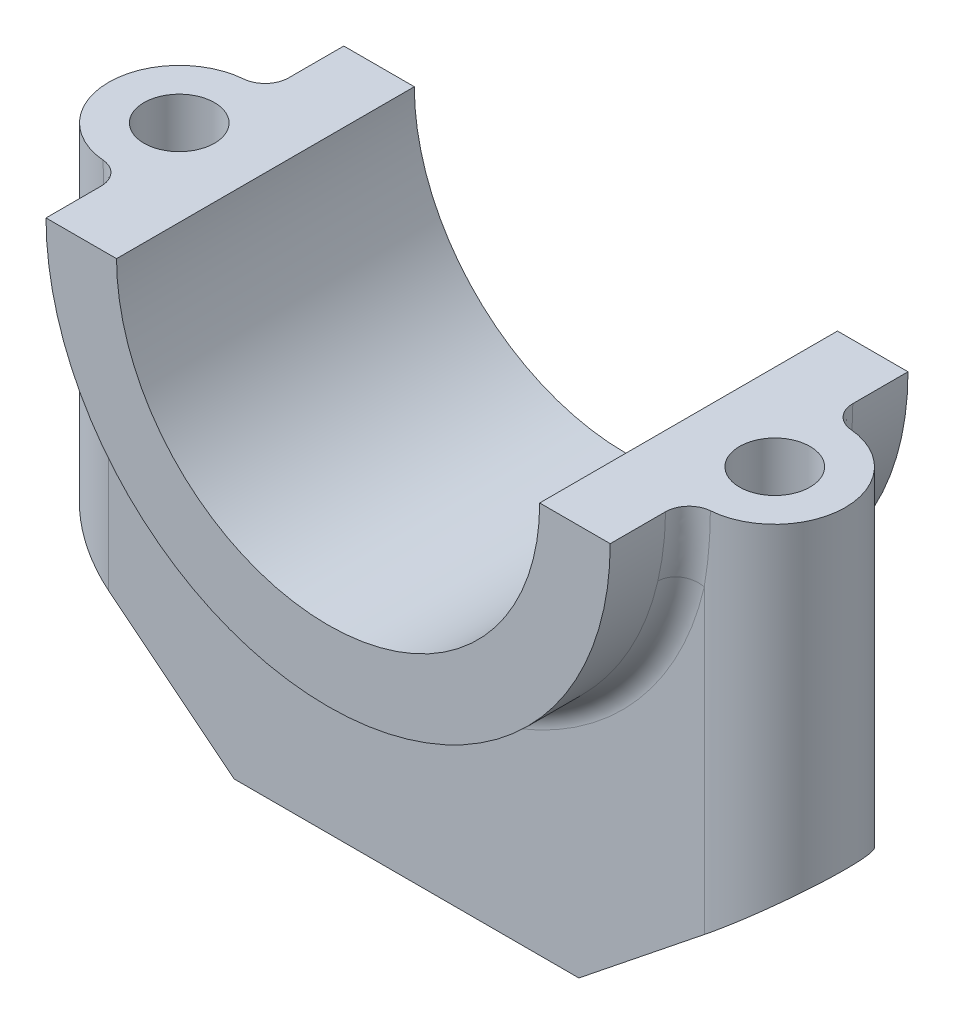
SolidWorks part; units mm, degrees
ref_plane "Front Plane" through (0, 0, 0) normal (0, 0, 1) x (1, 0, 0)
ref_plane "Top Plane" through (0, 0, 0) normal (0, 1, 0) x (1, 0, 0)
ref_plane "Right Plane" through (0, 0, 0) normal (1, 0, 0) x (0, 0, -1)
sketch "Sketch1" plane through (0, 0, 0) normal (0, 0, 1) x (1, 0, 0)
  line L0 (0, 0) -> (0, 17141.6634) construction
  line L1 (0, 0) -> (17141.6634, 0) construction
  line L2 (-47, 0) -> (47, 0)
  line L3 (47, 0) -> (47, -40)
  line L4 (47, -40) -> (22, -60)
  line L5 (22, -60) -> (-22, -60)
  line L6 (-47, -40) -> (-22, -60)
  line L7 (-47, 0) -> (-47, -40)
  arc A0 (-36, 0) -> (36, 0) centre (0, 0) ccw
  arc A1 (-27, 0) -> (27, 0) centre (0, 0) ccw
  point P11 (0, 0)
  point P15 (0, -60)
  point P16 (-1.8209, -32.4049)
  dimension "D1" = 72
  dimension "D2" = 54
  dimension "D3" = 25
  dimension "D4" = 60
  dimension "D5" = 20
  dimension "D6" = 47
extrude "Boss-Extrude1" add sketch "Sketch1" along normal mid plane 38 contours A1 L2 A0 region at (-31.5, -0.805, 0)
extrude "Boss-Extrude2" add sketch "Sketch1<3>" along normal mid plane 18 contours A0 L2 L7 L6 L5 L4 L3 region at (-41.5, -1.1152, 0)
sketch "Sketch1<3>" plane through (0, 0, 0) normal (0, 0, 1) x (1, 0, 0) same geometry as "Sketch1"
fillet "Fillet1" 2 edges at (47, -20, 9) (47, -20, -9) type full round first side face at (0, -29.5, 9) second side face at (0, -29.5, -9) middle face at (47, -20, 0)
fillet "Fillet2" 2 edges at (-47, -20, 9) (-47, -20, -9) type full round first side face at (-2.25, -30.4, 9) second side face at (-2.25, -30.4, -9) middle face at (-47, -20, 0)
hole_wizard "M10x1.5 Tapped Hole1" positions "3DSketch1" profile "Sketch2" tap size "M10x1.5" standard "ANSI Metric" end condition up to next
sketch3d "3DSketch1"
  line L0 (-38, 10.2622, 0) -> (-38, -20.5245, 0) construction
  line L1 (38, -36.9378, 0) -> (38, -67.7245, 0) construction
  point P0 (-38, 0, 0)
  point P4 (38, 0, 0)
sketch "Sketch2" plane through (-38, 0, 0) normal (1, 0, 0) x (0, 0, 1)
  line L0 (0, 0) -> (0, 47.2)
  line L1 (0, 47.2) -> (4.5, 47.2)
  line L2 (4.5, 47.2) -> (4.5, 0)
  line L5 (4.5, 0) -> (0, 0)
  line L11 (0, -6.35) -> (0, 107.95) construction
  dimension "Thru Tap Drill Dia." = 9
  dimension "Thru Tap Drill Depth" = 47.2
cosmetic thread "Hole Thread1" parameters "D2"=10
cosmetic thread "Hole Thread2" parameters "D2"=10
fillet "Fillet3" radius 3 2 edges at (0, -36, -9) (0, -36, 9)
